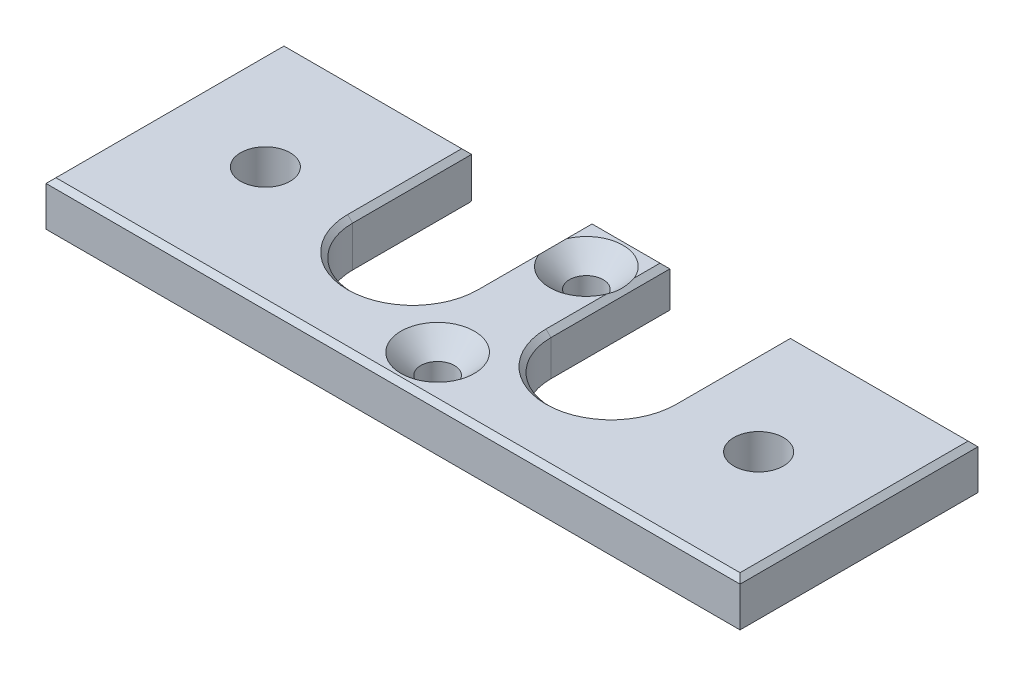
SolidWorks part; units mm, degrees
ref_plane "Front Plane" through (0, 0, 0) normal (0, 0, 1) x (1, 0, 0)
ref_plane "Top Plane" through (0, 0, 0) normal (0, 1, 0) x (1, 0, 0)
ref_plane "Right Plane" through (0, 0, 0) normal (1, 0, 0) x (0, 0, -1)
sketch "Sketch1" plane through (0, 0, 0) normal (0, 1, 0) x (1, 0, 0)
  line L0 (0, 0) -> (0, 50000) construction
  line L1 (35, -12) -> (-35, -12)
  line L2 (35, -12) -> (35, 12)
  line L3 (35, 12) -> (-35, 12)
  line L4 (-35, -12) -> (-35, 12)
  line L5 (35, -12) -> (-35, 12) construction
  line L6 (35, 12) -> (-35, -12) construction
  line L7 (0, 0) -> (50000, 0) construction
  line L8 (-16.075, 0) -> (-16.075, 12)
  line L9 (-3.925, 0) -> (-3.925, 12)
  line L10 (3.925, 0) -> (3.925, 12)
  line L11 (16.075, 0) -> (16.075, 12)
  circle A0 centre (-24.875, 0) radius 2.5
  circle A1 centre (-10, 0) radius 6.075
  circle A2 centre (24.875, 0) radius 2.5
  circle A3 centre (10, 0) radius 6.075
  circle A4 centre (0, -7.5) radius 1.7
  circle A5 centre (0, 7.5) radius 1.7
  point P0 (0, 0)
  dimension "D3" = 20
  dimension "D5" = 5
  dimension "D6" = 12.15
  dimension "D7" = 3.4
  dimension "D1" = 24
  dimension "D2" = 70
  dimension "D4" = 49.75
  dimension "D8" = 7.5
  dimension "D9" = 7.5
extrude "Boss-Extrude1" add sketch "Sketch1" along normal blind 5 contours L11 A3 L10 L3 L9 A1 L8 L4 L1 L2 A2 A0 region at (0, 0, 1.1939)
chamfer "Chamfer2" distance 2 angle 45 2 edges at (0, 5, -5.8) (0, 5, 9.2)
sketch "Sketch2" plane through (0, 0, 0) normal (0, -1, 0) x (1, 0, 0)
  line L9 (-1.525, 0) -> (-1.525, -12)
  line L10 (-18.475, -12) -> (-18.475, 0)
  line L11 (-1.525, 0) -> (-1.525, -12)
  line L12 (-18.475, -12) -> (-18.475, 0)
  line L14 (18.475, -12) -> (1.525, -12)
  line L15 (-1.525, -12) -> (-18.475, -12)
  line L16 (18.475, 0) -> (18.475, -12)
  line L17 (1.525, -12) -> (1.525, 0)
  line L18 (18.475, 0) -> (18.475, -12)
  line L19 (1.525, -12) -> (1.525, 0)
  arc A7 (-1.525, 0) -> (-18.475, 0) centre (-10, 0) ccw
  arc A8 (-1.525, 0) -> (-18.475, 0) centre (-10, 0) ccw
  arc A12 (18.475, 0) -> (1.525, 0) centre (10, 0) ccw
  arc A13 (18.475, 0) -> (1.525, 0) centre (10, 0) ccw
  dimension "D1" = 2.4
  dimension "D2" = 2.4
extrude "Cut-Extrude1" cut sketch "Sketch2" against normal blind 0.4
chamfer "Chamfer1" distance 0.5 angle 45 21 edges at (25.5375, 5, -12) (35, 5, 0) (0, 5, 12) (-35, 5, 0) (-25.5375, 5, -12) (-16.075, 5, -6) (-10, 5, 6.075) (-3.925, 5, -6) (0, 5, -12) (3.925, 5, -6) (10, 5, 6.075) (16.075, 5, -6) (26.7375, 0, -12) (35, 0, 0) (0, 0, 12) (-35, 0, 0) (-26.7375, 0, -12) (0, 0, -12) (3.925, 0.4, -6) (16.075, 0.4, -6) (10, 0.4, 6.075)
